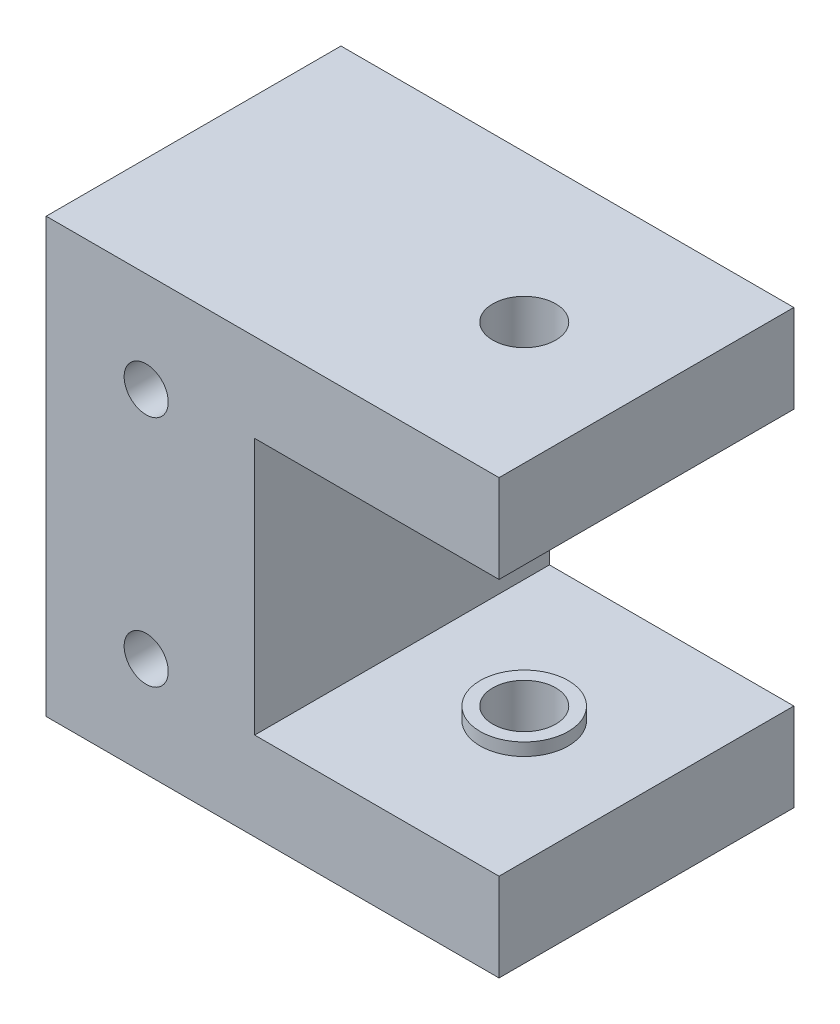
SolidWorks part; units mm, degrees
ref_plane "Front Plane" through (0, 0, 0) normal (0, 0, 1) x (1, 0, 0)
ref_plane "Top Plane" through (0, 0, 0) normal (0, 1, 0) x (1, 0, 0)
ref_plane "Right Plane" through (0, 0, 0) normal (1, 0, 0) x (0, 0, -1)
sketch "MainBlock" plane through (0, 0, 0) normal (0, 0, 1) x (1, 0, 0)
  line L0 (0, 0) -> (35.95, 0)
  line L1 (35.95, 0) -> (35.95, 7)
  line L2 (35.95, 7) -> (16.55, 7)
  line L3 (16.55, 7) -> (16.55, 27.4)
  line L4 (16.55, 27.4) -> (35.95, 27.4)
  line L5 (35.95, 27.4) -> (35.95, 34.4)
  line L6 (35.95, 34.4) -> (0, 34.4)
  line L7 (0, 34.4) -> (0, 0)
  circle A0 centre (7.9375, 26.4625) radius 1.75
  circle A1 centre (7.9375, 7.9375) radius 1.75
  dimension "D4" = 3.5
  dimension "D1" = 35.95
  dimension "D2" = 34.4
  dimension "D3" = 20.4
  dimension "D5" = 19.4
  dimension "D6" = 7.9375
  dimension "D7" = 7.9375
  dimension "D8" = 7.9375
extrude "MainBlockBoss-Extrude1" add sketch "MainBlock" along normal blind 23.4
sketch "TopHoleCut-Sketch2" plane through (0, 34.4, 0) normal (0, 1, 0) x (1, 0, 0)
  line L0 (35.95, 0) -> (0, 0) construction
  line L1 (0, -23.4) -> (0, 0) construction
  circle A0 centre (26.25, -11.7) radius 2.5
  dimension "D3" = 5
  dimension "D1" = 11.7
  dimension "D2" = 26.25
extrude "TopHoleCut-Extrude1" cut sketch "TopHoleCut-Sketch2" against normal blind 30
sketch "TopSpacerSketch4" plane through (0, 27.4, 0) normal (0, -1, 0) x (1, 0, 0)
  circle A0 centre (26.25, 11.7) radius 3.5
  circle A1 centre (26.25, 11.7) radius 2.5
  circle A2 centre (26.25, 11.7) radius 2.5 construction
  dimension "D1" = 7
extrude "TopSpacerBoss-Extrude2" add sketch "TopSpacerSketch4" along normal blind 1
sketch "LowerSpacerSketch5" plane through (0, 7, 0) normal (0, 1, 0) x (1, 0, 0)
  circle A0 centre (26.25, -11.7) radius 2.5
  circle A1 centre (26.25, -11.7) radius 2.5 construction
  circle A2 centre (26.25, -11.7) radius 3.5
  circle A3 centre (26.25, -11.7) radius 3.5 construction
extrude "LowerSpacerBoss-Extrude3" add sketch "LowerSpacerSketch5" along normal blind 1
sketch "MountHoleBoreSketch1" plane through (0, 0, 0) normal (0, 0, -1) x (-1, 0, 0)
  line L1 (-5.1875, 26.4625) -> (-6.5625, 28.8441)
  line L2 (-6.5625, 28.8441) -> (-9.3125, 28.8441)
  line L3 (-9.3125, 28.8441) -> (-10.6875, 26.4625)
  line L4 (-10.6875, 26.4625) -> (-9.3125, 24.0809)
  line L5 (-9.3125, 24.0809) -> (-6.5625, 24.0809)
  line L6 (-6.5625, 24.0809) -> (-5.1875, 26.4625)
  line L7 (-5.1875, 7.9375) -> (-6.5625, 10.3191)
  line L8 (-6.5625, 10.3191) -> (-9.3125, 10.3191)
  line L9 (-9.3125, 10.3191) -> (-10.6875, 7.9375)
  line L10 (-10.6875, 7.9375) -> (-9.3125, 5.5559)
  line L11 (-9.3125, 5.5559) -> (-6.5625, 5.5559)
  line L12 (-6.5625, 5.5559) -> (-5.1875, 7.9375)
  circle A0 centre (-7.9375, 26.4625) radius 2.3816 construction
  circle A1 centre (-7.9375, 7.9375) radius 2.3816 construction
  dimension "D1" = 5.5
extrude "MountHoleBoreCut-Extrude1" cut sketch "MountHoleBoreSketch1" against normal blind 2
sketch "PushPinHoleSketch1" plane through (0, 0, 0) normal (0, -1, 0) x (1, 0, 0)
  circle A0 centre (26.25, 11.7) radius 1
  circle A1 centre (26.25, 11.7) radius 2.5 construction
  dimension "D1" = 2
extrude "PushPinHoleCut-Extrude1" cut sketch "PushPinHoleSketch1" against normal through all
equation "\"BeltTensionerWidth\"= \"MidRailToAlignWithGantryBlock\" + \"BeltTensionerInnerWidth\" / 2"
equation "\"BeltTensionerHeight\"= \"BeltTensionerInnerHeight\" + \"BeltTensionerUpperLowerWallThickness\" * 2"
equation "\"BeltTensionerDepth\"= \"BeltTensionerBackWallThickness\" + \"BeltTensionerInnerDepth\"'Equals 23.4"
equation "\"BeltTensionerUpperLowerWallThickness\"= 7mm"
equation "\"BeltTensionerInnerWidth\"= \"20TGT2PulleyDiameter\" + \"BeltTensionerSpaceBetweenPulleyAndWall\""
equation "\"BeltTensionerInnerHeight\"= \"20TGT2PulleyWidth\" * 2 + \"1mmSpacer\" * 3"
equation "\"BeltTensionerBackWallThickness\"= 4mm"
equation "\"BeltTensionerInnerDepth\"= \"20TGT2PulleyDiameter\" + \"BeltTensionerSpaceBetweenPulleyAndWall\""
equation "\"RailThickness\"= .125in'Spec"
equation "\"HoleOffsetFromEdge\"= \"RailThickness\" * 2.5"
equation "\"LinearGBWithRailDepth\"= 12.75mm'Spec"
equation "\"GABDistanceFromBackToFirstPulley\"= 13.5mm"
equation "\"MidRailToAlignWithGantryBlock\"= \"LinearGBWithRailDepth\" + \"GABDistanceFromBackToFirstPulley\"'All outside cogs must align"
equation "\"20TGT2PulleyDiameter\"= 17.9mm'Spec"
equation "\"BeltTensionerSpaceBetweenPulleyAndWall\"= 1.5mm"
equation "\"BeltTensionerMountingHoleDiameter\"= 3.5mm'From the100"
equation "\"BeltTensionerMountingHoleOffsetFromEdge\"= \"HoleOffsetFromEdge\""
equation "\"20TGT2PulleyWidth\"= 8.7mm'The STL of the Pulley in the diagram is a bit larger"
equation "\"1mmSpacer\"= 1mm"
equation "\"SteelShaft5mmHoleDiameter\"= 5mm"
equation "\"BeltTensionerMountingHoleOuterBoreDepth\"= 2mm"
equation "\"BeltTensionerMountingHoleOuterBoreDiameter\"= 5.5mm'From the100"
equation "\"7mmx1mmSpacerDiameter\"= 7mm"
equation "\"7mmx1mmSpacerHeight\"= 1mm"
equation "\"D1@MainBlock\" = \"BeltTensionerWidth\""
equation "\"D2@MainBlock\" = \"BeltTensionerHeight\""
equation "\"D3@MainBlock\" = \"BeltTensionerInnerHeight\""
equation "\"D4@MainBlock\" = \"BeltTensionerMountingHoleDiameter\""
equation "\"D5@MainBlock\" = \"BeltTensionerInnerWidth\""
equation "\"D6@MainBlock\"=\"BeltTensionerMountingHoleOffsetFromEdge\""
equation "\"D7@MainBlock\" = \"HoleOffsetFromEdge\""
equation "\"D8@MainBlock\" = \"HoleOffsetFromEdge\""
equation "\"D1@MainBlockBoss-Extrude1\" = \"BeltTensionerDepth\""
equation "\"D1@TopHoleCut-Sketch2\" = \"BeltTensionerDepth\" / 2"
equation "\"D2@TopHoleCut-Sketch2\" = \"MidRailToAlignWithGantryBlock\""
equation "\"D3@TopHoleCut-Sketch2\" = \"SteelShaft5mmHoleDiameter\""
equation "\"D1@TopSpacerSketch4\" = \"7mmx1mmSpacerDiameter\""
equation "\"D1@TopSpacerBoss-Extrude2\" = \"7mmx1mmSpacerHeight\""
equation "\"D1@LowerSpacerBoss-Extrude3\" = \"7mmx1mmSpacerHeight\""
equation "\"D1@MountHoleBoreSketch1\" = \"BeltTensionerMountingHoleOuterBoreDiameter\""
equation "\"D1@MountHoleBoreCut-Extrude1\" = \"BeltTensionerMountingHoleOuterBoreDepth\""
equation "\"StealPinPushHoleDiameter\" = 2mm"
equation "\"D1@PushPinHoleSketch1\" = \"StealPinPushHoleDiameter\""
